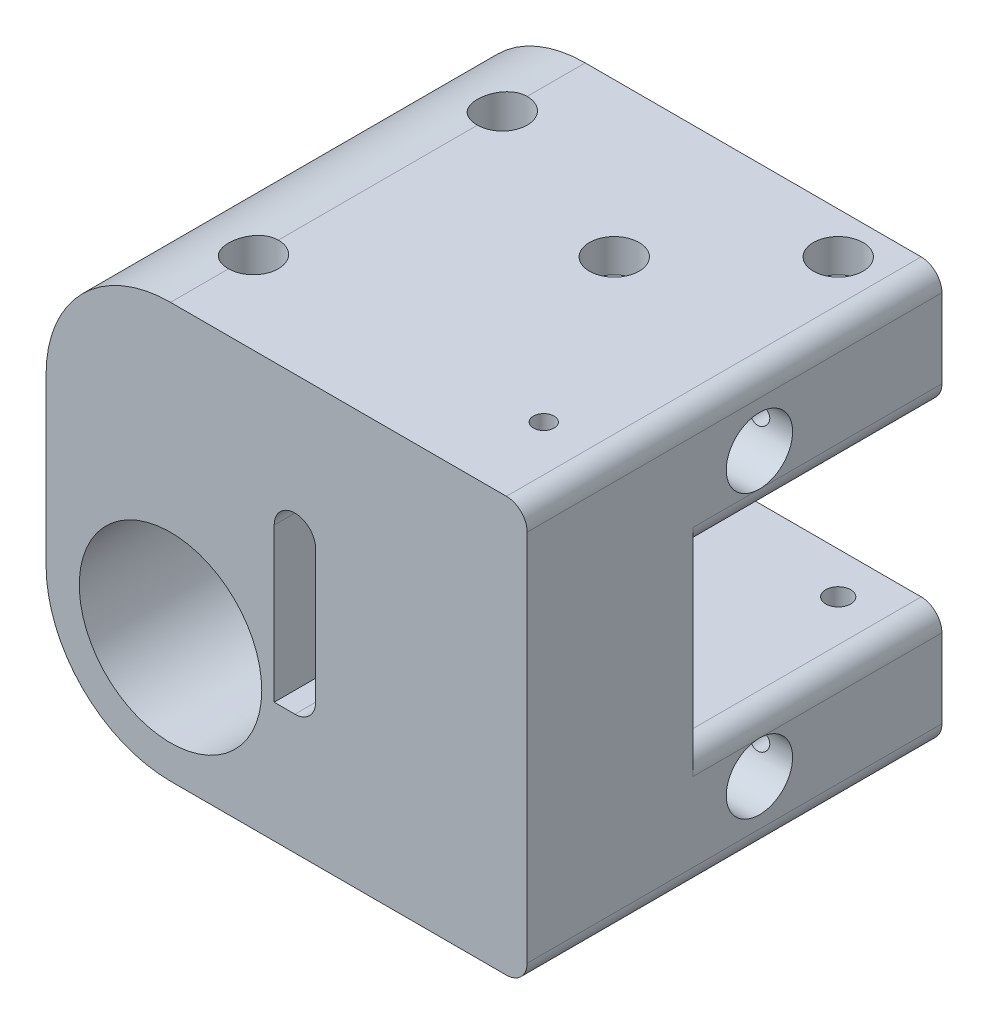
SolidWorks part; units mm, degrees
material "PLA"
ref_plane "Front Plane" through (0, 0, 0) normal (0, 0, 1) x (1, 0, 0)
ref_plane "Top Plane" through (0, 0, 0) normal (0, 1, 0) x (1, 0, 0)
ref_plane "Right Plane" through (0, 0, 0) normal (1, 0, 0) x (0, 0, -1)
sketch "Sketch1" plane through (0, 0, 0) normal (0, 0, 1) x (1, 0, 0)
  line L1 (0, 0) -> (58, 0)
  line L2 (0, 0) -> (0, 50)
  line L3 (0, 50) -> (58, 50)
  line L4 (58, 0) -> (58, 50)
  circle A0 centre (15, 15) radius 11
  dimension "D1" = 22
  dimension "D2" = 58
  dimension "D3" = 15
  dimension "D4" = 50
  dimension "D5" = 15
extrude "Boss-Extrude1" add sketch "Sketch1" along normal blind 50
sketch "Sketch2" plane through (58, 0, 0) normal (-1, 0, 0) x (0, 0, 1)
  line L0 (50, 50) -> (0, 50) construction
  line L1 (50, 0) -> (0, 0) construction
  line L2 (0, 0) -> (0, 50) construction
  circle A0 centre (22, 42) radius 4
  circle A1 centre (22, 8) radius 4
  dimension "D1" = 8
  dimension "D2" = 8
  dimension "D3" = 8
  dimension "D4" = 22
extrude "Cut-Extrude1" cut sketch "Sketch2" along normal blind 20
sketch "Sketch3" plane through (0, 0, 0) normal (0, 0, -1) x (-1, 0, 0)
  line L10 (-32.5, 14.5) -> (-27.5, 14.5)
  line L11 (-32.5, 14.5) -> (-32.5, 35.5)
  line L12 (-32.5, 35.5) -> (-27.5, 35.5)
  line L13 (-27.5, 14.5) -> (-27.5, 35.5)
  line L17 (-29.5, 32.4) -> (-29.5, 26.4) construction
  line L19 (0, 0) -> (-58, 0) construction
  circle A0 centre (-15, 15) radius 10.5 construction
  point P0 (-30, 21.9)
  point P9 (-30, 21.9)
  dimension "D1" = 14.5
  dimension "D2" = 5
  dimension "D3" = 2
  dimension "D4" = 21
extrude "Cut-Extrude2" cut sketch "Sketch3" against normal through all
sketch "Sketch14" plane through (0, 0, 0) normal (0, 0, -1) x (-1, 0, 0)
  line L0 (-58, 0) -> (-58, 50) construction
  line L5 (-32.5, 14.5) -> (-58, 14.5)
  line L6 (-32.5, 14.5) -> (-32.5, 35.5)
  line L7 (-32.5, 35.5) -> (-58, 35.5)
  line L8 (-58, 14.5) -> (-58, 35.5)
  line L9 (0, 0) -> (-58, 0) construction
  dimension "D1" = 14.5
  dimension "D2" = 21
extrude "Cut-Extrude9" cut sketch "Sketch14" against normal blind 30
sketch "Sketch16" plane through (0, 50, 0) normal (0, 1, 0) x (1, 0, 0)
  line L3 (58, 0) -> (0, 0) construction
  circle A0 centre (50.5, -5) radius 1.5
  circle A1 centre (37, -18.5) radius 1.5
  dimension "D1" = 3
  dimension "D3" = 5
  dimension "D2" = 13.5
  dimension "D4" = 13.5
extrude "Cut-Extrude10" cut sketch "Sketch16" against normal blind 57
sketch "Sketch17" plane through (0, 0, 0) normal (0, -1, 0) x (1, 0, 0)
  line L1 (38.6166, 15.7) -> (40.2332, 18.5)
  line L2 (40.2332, 18.5) -> (38.6166, 21.3)
  line L3 (38.6166, 21.3) -> (35.3834, 21.3)
  line L4 (35.3834, 21.3) -> (33.7668, 18.5)
  line L5 (33.7668, 18.5) -> (35.3834, 15.7)
  line L6 (35.3834, 15.7) -> (38.6166, 15.7)
  line L7 (53.7332, 5) -> (52.1166, 7.8)
  line L8 (52.1166, 7.8) -> (48.8834, 7.8)
  line L9 (48.8834, 7.8) -> (47.2668, 5)
  line L10 (47.2668, 5) -> (48.8834, 2.2)
  line L11 (48.8834, 2.2) -> (52.1166, 2.2)
  line L12 (52.1166, 2.2) -> (53.7332, 5)
  circle A0 centre (37, 18.5) radius 2.8 construction
  circle A1 centre (50.5, 5) radius 2.8 construction
  dimension "D1" = 5.6
extrude "Cut-Extrude11" cut sketch "Sketch17" against normal blind 3
fillet "Fillet3" radius 15 2 edges at (0, 50, 25) (0, 0, 25)
sketch "Sketch18" plane through (0, 0, 0) normal (0, 0, -1) x (-1, 0, 0)
  line L0 (-58, 35.5) -> (-58, 50) construction
  line L1 (-58, 50) -> (-15, 50) construction
  line L2 (-15, 0) -> (-58, 0) construction
  circle A0 centre (-54, 42) radius 1.25
  circle A1 centre (-54, 8) radius 1.25
  dimension "D1" = 2.5
  dimension "D2" = 4
  dimension "D4" = 8
  dimension "D3" = 8
extrude "Cut-Extrude12" cut sketch "Sketch18" against normal up to next
sketch "Sketch19" plane through (0, 50, 0) normal (0, 1, 0) x (1, 0, 0)
  line L1 (58, -50) -> (15, -50) construction
  line L2 (58, 0) -> (15, 0) construction
  circle A0 centre (15, -10) radius 1.25
  circle A1 centre (15, -40) radius 1.25
  dimension "D1" = 2.5
  dimension "D2" = 15
  dimension "D5" = 10
  dimension "D4" = 10
extrude "Cut-Extrude13" cut sketch "Sketch19" against normal up to next
sketch "Sketch20" plane through (0, 50, 0) normal (0, 1, 0) x (1, 0, 0)
  circle A0 centre (15, -10) radius 3
  circle A2 centre (15, -40) radius 3
  dimension "D1" = 6
extrude "Cut-Extrude14" cut sketch "Sketch20" against normal blind 10
sketch "Sketch21" plane through (0, 0, 0) normal (0, 0, -1) x (-1, 0, 0)
  circle A0 centre (-54, 42) radius 3
  circle A1 centre (-54, 8) radius 3
  dimension "D1" = 6
extrude "Cut-Extrude15" cut sketch "Sketch21" against normal blind 3
fillet "Fillet4" radius 2.5 7 edges at (32.5, 35.5, 40) (32.5, 14.5, 40) (58, 0, 25) (58, 14.5, 15) (27.5, 35.5, 25) (58, 35.5, 15) (58, 50, 25)
sketch "Sketch22" plane through (38, 0, 0) normal (1, 0, 0) x (0, 0, -1)
  circle A0 centre (-22, 42) radius 1.25
  dimension "D1" = 2.5
extrude "Cut-Extrude16" cut sketch "Sketch22" against normal through all
sketch "Sketch23" plane through (0, 0, 0) normal (-1, 0, 0) x (0, 0, 1)
  circle A0 centre (22, 42) radius 3
  dimension "D1" = 6
extrude "Cut-Extrude17" cut sketch "Sketch23" against normal blind 10
sketch "Sketch24" plane through (0, 50, 0) normal (0, 1, 0) x (1, 0, 0)
  circle A0 centre (50.5, -5) radius 3
  circle A1 centre (37, -18.5) radius 3
  dimension "D1" = 6
extrude "Cut-Extrude18" cut sketch "Sketch24" against normal blind 4
sketch "Sketch25" plane through (0, 50, 0) normal (0, 1, 0) x (1, 0, 0)
  line L0 (55.5, -50) -> (15, -50) construction
  line L1 (58, 0) -> (58, -50) construction
  circle A0 centre (50, -40) radius 1.25
  dimension "D1" = 2.5
  dimension "D2" = 10
  dimension "D3" = 8
extrude "Cut-Extrude19" cut sketch "Sketch25" against normal blind 10
sketch "Sketch26" plane through (0, 35.5, 0) normal (0, -1, 0) x (1, 0, 0)
  circle A0 centre (50.5, 5) radius 3
  circle A1 centre (50.5, 5) radius 1.5
  dimension "D1" = 6
extrude "Boss-Extrude2" add sketch "Sketch26" along normal blind 1
sketch "Sketch27" plane through (0, 14.5, 0) normal (0, 1, 0) x (1, 0, 0)
  circle A0 centre (37, -18.5) radius 1.5
  circle A1 centre (37, -18.5) radius 3
extrude "Boss-Extrude3" add sketch "Sketch27" along normal blind 1
chamfer "Chamfer1" distance 1 angle 45 2 edges at (50.5, 34.5, 2) (34, 15.5, 18.5)
sketch "Sketch28" plane through (0, 0, 0) normal (0, 0, -1) x (-1, 0, 0)
  circle A0 centre (-20.0889, 34.9) radius 1.25
  dimension "D1" = 2.5
extrude "Cut-Extrude20" cut sketch "Sketch28" against normal blind 10
chamfer "Chamfer2" distance 1.5 angle 45 1 edges at (18.8389, 34.9, 0)
